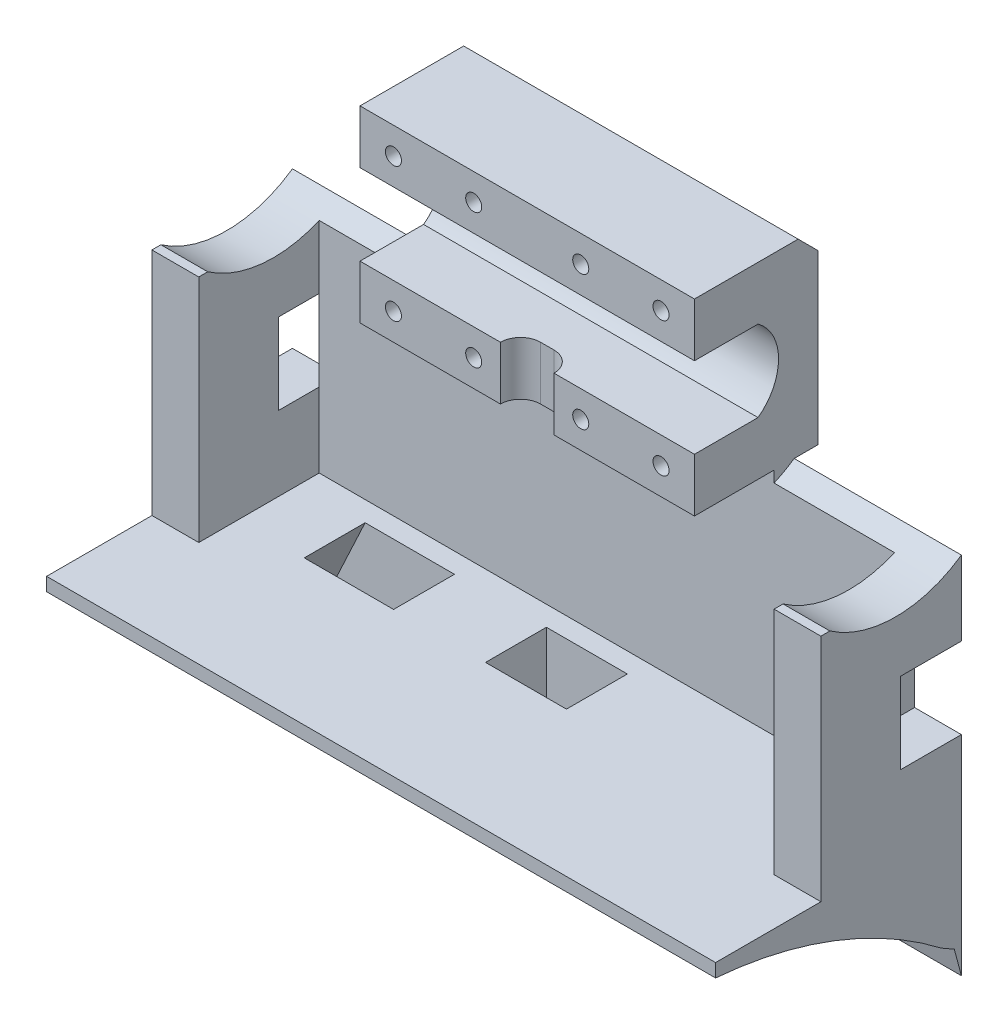
SolidWorks part; units mm, degrees
material "PLA"
ref_plane "Front Plane" through (0, 0, 0) normal (0, 0, 1) x (1, 0, 0)
ref_plane "Top Plane" through (0, 0, 0) normal (0, 1, 0) x (1, 0, 0)
ref_plane "Right Plane" through (0, 0, 0) normal (1, 0, 0) x (0, 0, -1)
sketch "Croquis1" plane through (0, 0, 0) normal (0, 0, 1) x (1, 0, 0)
  line L1 (-50, -48) -> (50, -48)
  line L2 (-50, -48) -> (-50, 19.9)
  line L3 (-25, 48) -> (25, 48)
  line L4 (50, -48) -> (50, 19.9)
  line L5 (-50, 19.9) -> (-25, 19.9)
  line L6 (-25, 19.9) -> (-25, 48)
  line L8 (50, 19.9) -> (25, 19.9)
  line L9 (25, 19.9) -> (25, 48)
  point P0 (0, 0)
  dimension "D1" = 96
  dimension "D2" = 25
  dimension "D3" = 28.1
  dimension "D4" = 25
  dimension "D5" = 50
extrude "Base" add sketch "Croquis1" along normal blind 3
sketch "Croquis2" plane through (0, 0, 3) normal (0, 0, 1) x (1, 0, 0)
  line L1 (-25, 48) -> (25, 48)
  line L2 (-25, 48) -> (-25, 19.9)
  line L3 (-25, 19.9) -> (25, 19.9)
  line L4 (25, 48) -> (25, 19.9)
extrude "Saliente-Extruir2" add sketch "Croquis2" along normal blind 15.5
sketch "Croquis3" plane through (-25, 0, 0) normal (-1, 0, 0) x (0, 0, 1)
  line L0 (18.5, 40) -> (18.5, 27.9)
  line L1 (18.5, 48) -> (18.5, 19.9) construction
  line L2 (18.5, 40) -> (9, 40)
  line L3 (18.5, 27.9) -> (9, 27.9)
  arc A2 (9, 40) -> (9, 27.9) centre (13.43, 33.95) ccw
  dimension "D3" = 7.4985
  dimension "D1" = 12.1
  dimension "D2" = 8
  dimension "D4" = 9.5
extrude "Cortar-Extruir1" cut sketch "Croquis3" against normal up to next
sketch "Croquis4" plane through (0, 19.9, 0) normal (0, -1, 0) x (1, 0, 0)
  line L1 (-25, 18.5) -> (25, 18.5) construction
  line L2 (1, 15.5) -> (-1, 15.5)
  line L3 (4, 18.5) -> (-4, 18.5)
  arc A0 (-4, 18.5) -> (-1, 15.5) centre (-1, 18.5) ccw
  arc A1 (4, 18.5) -> (1, 15.5) centre (1, 18.5) cw
  point P0 (0, 18.5)
  point P1 (0, 15.5)
  dimension "D1" = 4
  dimension "D4" = 3
  dimension "D2" = 3
  dimension "D3" = 1
extrude "Cortar-Extruir2" cut sketch "Croquis4" against normal up to next
sketch "Croquis5" plane through (0, 0, 18.5) normal (0, 0, 1) x (1, 0, 0)
  circle A0 centre (-20, 44) radius 1.2
  circle A1 centre (-8, 44) radius 1.2
  circle A2 centre (-20, 23.9) radius 1.2
  circle A3 centre (-8, 23.9) radius 1.2
  circle A4 centre (8, 44) radius 1.2
  circle A5 centre (20, 44) radius 1.2
  circle A6 centre (8, 23.9) radius 1.2
  circle A7 centre (20, 23.9) radius 1.2
  point P2 (-8, 44)
  point P3 (-8, 23.9)
  point P4 (-20, 23.9)
  point P5 (-20, 44)
  point P10 (20, 44)
  point P11 (20, 23.9)
  point P12 (8, 23.9)
  point P13 (8, 44)
  dimension "D1" = 2
  dimension "D2" = 2
sketch "Croquis15" plane through (0, 0, 3) normal (0, 0, 1) x (1, 0, 0)
  line L1 (-50, 19.9) -> (50, 19.9)
  line L2 (-50, 19.9) -> (-50, -34.56)
  line L3 (-50, -34.56) -> (50, -34.56)
  line L4 (50, 19.9) -> (50, -34.56)
  dimension "D1" = 100
extrude "Saliente-Extruir3" add sketch "Croquis15" along normal blind 3.6
sketch "Croquis16" plane through (0, 0, 0) normal (0, 0, -1) x (-1, 0, 0)
  line L0 (25, 19.9) -> (50, 19.9)
  line L1 (-50, 19.9) -> (-25, 19.9)
  line L2 (-50, 19.9) -> (-50, -48)
  line L3 (-50, -48) -> (50, -48)
  line L4 (50, 19.9) -> (50, -48)
  line L9 (-25, 19.9) -> (25, 19.9)
extrude "Cortar-Extruir3" cut sketch "Croquis16" against normal blind 3.6
extrude "Cortar-Extruir4" cut sketch "Croquis5" against normal blind 4
sketch "Croquis22" plane through (-50, 0, 0) normal (-1, 0, 0) x (0, 0, 1)
  line L1 (4.66, -30.6) -> (6.6, -29.4799)
  line L5 (6.6, 19.9) -> (6.6, -34.56) construction
  line L7 (6.6, -34.56) -> (3.6, -34.56)
  line L8 (4.66, -30.6) -> (3.6, -34.56)
  line L9 (6.6, -29.4799) -> (6.6, -34.56)
  dimension "D2" = 3.96
  dimension "D3" = 3
extrude "Cortar-Extruir7" cut sketch "Croquis22" against normal through all
sketch "Croquis24" plane through (-50, 0, 0) normal (-1, 0, 0) x (0, 0, 1)
  line L18 (24.6, -14.4799) -> (40.3453, -14.4799)
  line L21 (40.3453, -16.4799) -> (40.3453, -14.4799)
  line L25 (6.6, 19.9) -> (24.6, 19.9)
  line L26 (24.6, 19.9) -> (24.6, -14.4799)
  line L33 (6.6, 19.9) -> (6.6, -29.4799)
  arc A1 (6.6, -29.4799) -> (40.3453, -16.4799) centre (45.6277, -80.4899) cw
  point P13 (11.15, 2.71)
  dimension "D1" = 2
extrude "Saliente-Extruir5" add sketch "Croquis24" against normal through all
chamfer "Chaflán1" distance 3 angle 45 1 edges at (0, 48, 0)
sketch "Croquis25" plane through (-50, 0, 0) normal (-1, 0, 0) x (0, 0, 1)
  line L1 (23.26, 19.9) -> (3.6, 19.9)
  line L4 (24.6, 19.9) -> (3.6, 19.9) construction
  arc A2 (3.6, 19.9) -> (23.26, 19.9) centre (13.43, 33.95) ccw
extrude "Cortar-Extruir9" cut sketch "Croquis25" against normal blind 25
sketch "Croquis26" plane through (50, 0, 0) normal (1, 0, 0) x (0, 0, -1)
  line L1 (-3.6, 19.9) -> (-23.26, 19.9)
  arc A0 (-23.26, 19.9) -> (-3.6, 19.9) centre (-13.43, 33.95) ccw
extrude "Cortar-Extruir10" cut sketch "Croquis26" against normal blind 25
sketch "Croquis28" plane through (0, 0, 24.6) normal (0, 0, 1) x (1, 0, 0)
  line L0 (50, 19.9) -> (-50, 19.9) construction
  line L4 (-43, -9.4799) -> (-43, 19.9)
  line L9 (43, -9.4799) -> (43, 19.9)
  line L10 (-43, 19.9) -> (43, 19.9)
  line L11 (-43, -9.4799) -> (-43, -14.4799)
  line L12 (50, -14.4799) -> (-50, -14.4799) construction
  line L13 (-43, -14.4799) -> (43, -14.4799)
  line L14 (43, -14.4799) -> (43, -9.4799)
extrude "Cortar-Extruir11" cut sketch "Croquis28" against normal blind 18
sketch "Croquis30" plane through (-50, 0, 0) normal (-1, 0, 0) x (0, 0, 1)
  line L4 (12.7, -3.34) -> (3.6, -3.34)
  line L5 (12.7, -3.34) -> (12.7, 8.76)
  line L6 (12.7, 8.76) -> (3.6, 8.76)
  line L7 (3.6, -3.34) -> (3.6, 8.76)
  point P6 (8.15, 2.71)
extrude "Cortar-Extruir12" cut sketch "Croquis30" against normal blind 7
sketch "Croquis31" plane through (50, 0, 0) normal (1, 0, 0) x (0, 0, -1)
  line L4 (-12.7, -3.34) -> (-3.6, -3.34)
  line L5 (-12.7, -3.34) -> (-12.7, 8.76)
  line L6 (-12.7, 8.76) -> (-3.6, 8.76)
  line L7 (-3.6, -3.34) -> (-3.6, 8.76)
  point P6 (-8.15, 2.71)
extrude "Cortar-Extruir13" cut sketch "Croquis31" against normal blind 7
sketch "Croquis32" plane through (0, 0, 6.6) normal (0, 0, 1) x (1, 0, 0)
  line L0 (-50, -7.2846) -> (0, -30.6)
  line L1 (-50, -14.4799) -> (-50, 19.9) construction
  line L2 (50, -30.6) -> (-50, -30.6) construction
  line L3 (50, -29.4799) -> (-50, -29.4799) construction
  dimension "D1" = 25
sketch "Croquis33" plane through (-50, 0, 0) normal (-1, 0, 0) x (0, 0, 1)
  line L0 (6.6, -7.2846) -> (27.4829, -7.2846)
  line L3 (6.6, -7.2846) -> (6.6, -30.6) construction
ref_plane "Plano1" through (-11.7205, -25.1347, 0) normal (-0.4226, -0.9063, 0) x (-0.9063, 0.4226, 0)
sketch "Croquis36" plane through (-11.7205, -25.1347, 0) normal (-0.4226, -0.9063, 0) x (-0.9063, 0.4226, 0)
  line L2 (11.8066, -9.6) -> (23.9066, -9.6)
  line L6 (11.8066, -9.6) -> (11.8066, -18.7)
  line L7 (11.8066, -18.7) -> (23.9066, -18.7)
  line L8 (23.9066, -9.6) -> (23.9066, -18.7)
extrude "Cortar-Extruir14" cut sketch "Croquis36" against normal blind 7 and the other way through all
sketch "Croquis37" plane through (0, -14.4799, 0) normal (0, 1, 0) x (1, 0, 0)
  line L3 (-6.05, -9.584) -> (6.05, -9.584)
  line L5 (-6.05, -9.584) -> (-6.05, -18.684)
  line L6 (-6.05, -18.684) -> (6.05, -18.684)
  line L7 (6.05, -9.584) -> (6.05, -18.684)
extrude "Cortar-Extruir15" cut sketch "Croquis37" against normal through all
